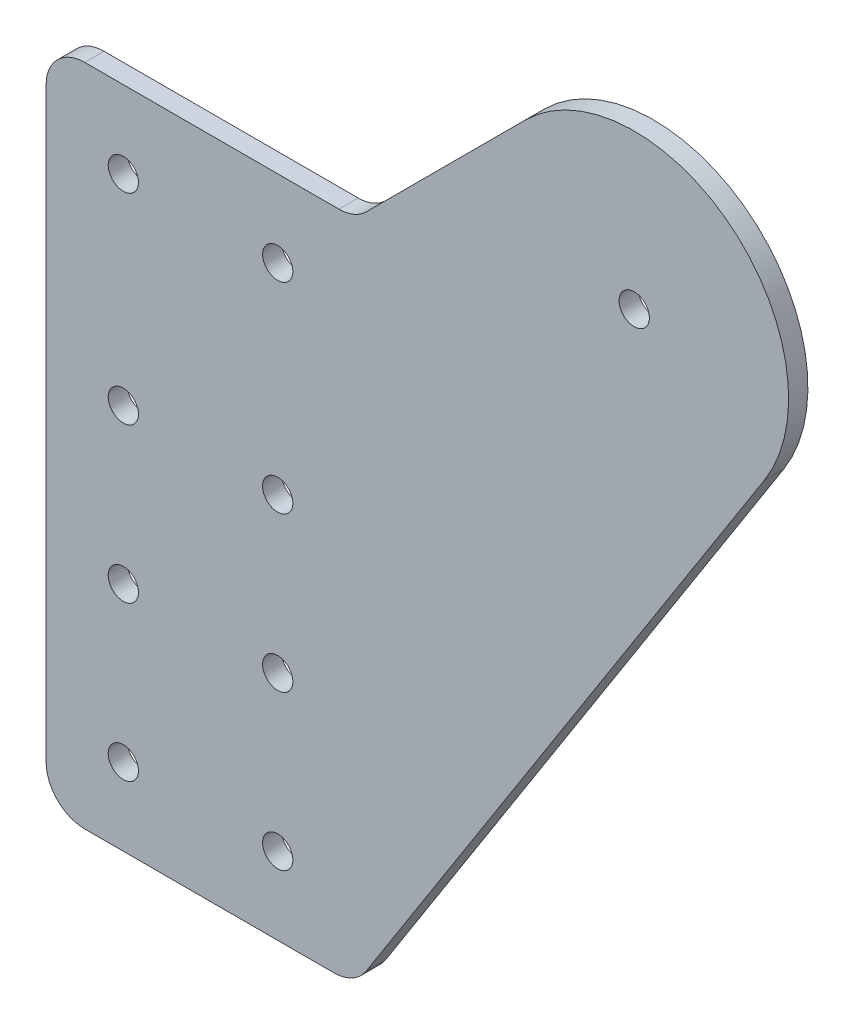
SolidWorks part; units mm, degrees
material "6061-T6 (SS)"
ref_plane "Front Plane" through (0, 0, 0) normal (0, 0, 1) x (1, 0, 0)
ref_plane "Top Plane" through (0, 0, 0) normal (0, 1, 0) x (1, 0, 0)
ref_plane "Right Plane" through (0, 0, 0) normal (1, 0, 0) x (0, 0, -1)
sketch "Sketch2" plane through (0, 0, 0) normal (0, 0, 1) x (1, 0, 0)
  line L0 (50.8, 109.22) -> (78.7932, 137.2132)
  line L1 (0, 0) -> (50.8, 0)
  line L2 (0, 0) -> (0, 109.22)
  line L3 (0, 109.22) -> (50.8, 109.22)
  line L5 (50.8, 0) -> (118.1669, 105.5912)
  arc A1 (118.1669, 105.5912) -> (78.7932, 137.2132) centre (96.7537, 119.2527) ccw
  circle A2 centre (96.7537, 119.2527) radius 2.4892
  dimension "D3" = 50.8
  dimension "D4" = 4.9784
  dimension "D1" = 50.8
  dimension "D2" = 109.22
extrude "Boss-Extrude1" add sketch "Sketch2" against normal blind 3.175
sketch "Sketch3" plane through (0, 0, 0) normal (0, 0, 1) x (1, 0, 0)
  line L0 (50.8, 109.22) -> (0, 109.22) construction
  line L1 (0, 109.22) -> (0, 0) construction
  circle A0 centre (12.7, 96.52) radius 2.4892
  circle A17 centre (38.1, 96.52) radius 2.4892
  circle A24 centre (12.7, 63.5) radius 2.4892
  circle A25 centre (12.7, 38.1) radius 2.4892
  circle A26 centre (12.7, 12.7) radius 2.4892
  circle A27 centre (12.7, -12.7) radius 2.4892
  circle A28 centre (12.7, -38.1) radius 2.4892
  circle A33 centre (38.1, 38.1) radius 2.4892
  circle A34 centre (38.1, 12.7) radius 2.4892
  circle A35 centre (38.1, -12.7) radius 2.4892
  circle A36 centre (38.1, -38.1) radius 2.4892
  circle A41 centre (38.1, 63.5) radius 2.4892
  dimension "D1" = 4.9784
  dimension "D6" = 4.9784
  dimension "D2" = 12.7
  dimension "D3" = 12.7
  dimension "D7" = 12.7
  dimension "D8" = 33.02
  dimension "D4" = 1
  dimension "D5" = 2
  dimension "D9" = 5
  dimension "D10" = 2
extrude "Cut-Extrude1" cut sketch "Sketch3" against normal through all
fillet "Fillet1" radius 6.35 4 edges at (0, 0, -1.5875) (50.8, 0, -1.5875) (50.8, 109.22, -1.5875) (0, 109.22, -1.5875)
